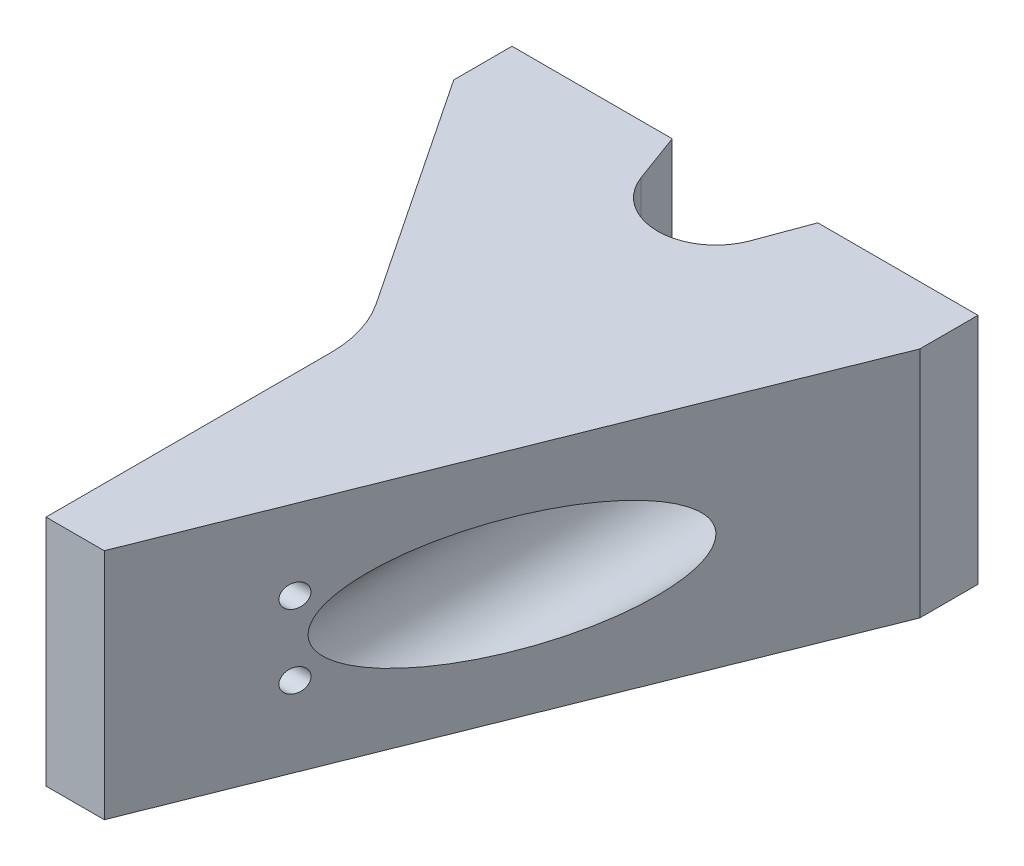
SolidWorks part; units mm, degrees
material "PET"
ref_plane "Front" through (0, 0, 0) normal (0, 0, 1) x (1, 0, 0)
ref_plane "Top" through (0, 0, 0) normal (0, 1, 0) x (1, 0, 0)
ref_plane "Right" through (0, 0, 0) normal (1, 0, 0) x (0, 0, -1)
sketch "Sketch1" plane through (0, 0, 0) normal (0, 1, 0) x (1, 0, 0)
  line L0 (0, 0) -> (17.4625, 0)
  line L1 (50.8, 0) -> (50.8, -6.35)
  line L3 (50.8, -6.35) -> (25.4, -69.85)
  line L4 (25.4, -69.85) -> (19.05, -69.85)
  line L5 (0, -6.35) -> (0, 0)
  line L6 (17.4625, 0) -> (19.4417, -5.3707)
  line L7 (31.3583, -5.3707) -> (33.3375, 0)
  line L8 (33.3375, 0) -> (50.8, 0)
  line L9 (19.05, -69.85) -> (19.05, -38.7703)
  line L10 (16.917, -31.7256) -> (0, -6.35)
  arc A0 (19.4417, -5.3707) -> (31.3583, -5.3707) centre (25.4, -3.175) ccw
  arc A1 (19.05, -38.7703) -> (16.917, -31.7256) centre (6.35, -38.7703) ccw
  point P5 (17.2123, -39.0598)
  point P13 (30.48, -3.81)
  point P14 (20.32, -3.81)
  point P15 (0, 0)
  point P16 (25.4, 0)
  point P20 (19.05, -34.925)
  dimension "D6" = 6.35
  dimension "D7" = 9.525
  dimension "D10" = 12.7
  dimension "D1" = 50.8
  dimension "D2" = 6.35
  dimension "D3" = 69.85
  dimension "D4" = 31.75
  dimension "D5" = 34.925
  dimension "D8" = 15.875
  dimension "D9" = 6.35
extrude "Boss-Extrude1" add sketch "Sketch1" along normal mid plane 25.4
sketch "Sketch2" plane through (0, 0, 0) normal (0, 1, 0) x (1, 0, 0)
  line L0 (12.7, 0) -> (12.7, -117.475)
  line L1 (17.4625, 0) -> (0, 0) construction
  line L2 (12.7, -117.475) -> (6.35, -117.475)
  line L3 (6.35, -117.475) -> (6.35, -9.525)
  line L4 (6.35, -9.525) -> (10.1473, -9.525)
  line L5 (10.1473, -9.525) -> (10.1473, 0)
  line L6 (10.1473, 0) -> (12.7, 0)
  line L7 (12.7, 0) -> (12.7, 3.0151) construction
  line L8 (25.4, -3.175) -> (25.4, 4.4959) construction
  line L9 (25.4, -69.85) -> (50.8, -6.35) construction
  point P12 (6.35, -61.6857)
  dimension "D1" = 5.1054
  dimension "D2" = 9.525
  dimension "D3" = 12.7
  dimension "D4" = 25.4
revolve "Cut-Revolve1" cut sketch "Sketch2" angle 360 about L7
pattern_linear "LPattern1" count 2 spacing 25.4 along (1, 0, 0) of "Cut-Revolve1"
sketch "Sketch5" plane through (19.05, 0, 0) normal (-1, 0, 0) x (0, 0, 1)
  line L0 (55, 4) -> (55, 12.7) construction
  line L1 (38.7703, 12.7) -> (69.85, 12.7) construction
  line L6 (55, -4) -> (55, -12.7) construction
  line L7 (38.7703, -12.7) -> (69.85, -12.7) construction
  line L9 (0, 12.7) -> (0, -12.7) construction
  point P0 (55, 4)
  point P2 (55, -4)
  dimension "D1" = 55
  dimension "D2" = 8
hole_wizard "M3x0.5 Tapped Hole1" positions "Sketch5" profile "Sketch4" tap size "M3x0.5" standard "ANSI Metric" end condition through all
sketch "Sketch4" plane through (19.05, 4, 55) normal (0, 1, 0) x (0, 0, 1)
  line L0 (0, 0) -> (0, 31.75)
  line L1 (0, 31.75) -> (1.25, 31.75)
  line L2 (1.25, 31.75) -> (1.25, 0)
  line L5 (1.25, 0) -> (0, 0)
  line L11 (0, -6.35) -> (0, 107.95) construction
  dimension "Thru Tap Drill Dia." = 2.5
  dimension "Thru Tap Drill Depth" = 31.75
cosmetic thread "Hole Thread1" parameters "D2"=3
cosmetic thread "Hole Thread2" parameters "D2"=3
